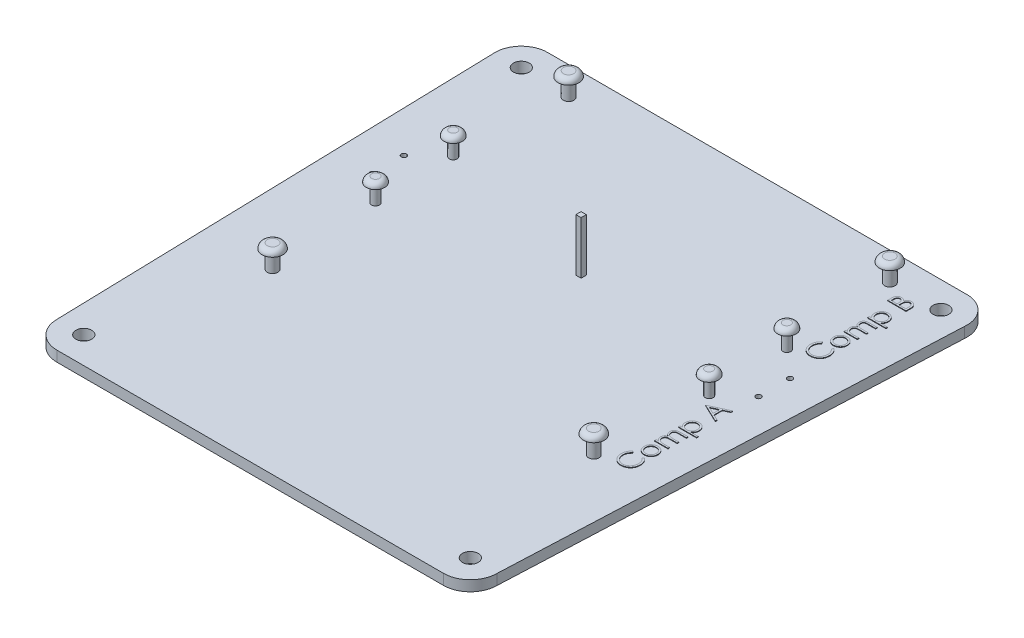
SolidWorks part; units mm, degrees
material "A-Glass Fiber"
ref_plane "Front Plane" through (0, 0, 0) normal (0, 0, 1) x (1, 0, 0)
ref_plane "Top Plane" through (0, 0, 0) normal (0, 1, 0) x (1, 0, 0)
ref_plane "Right Plane" through (0, 0, 0) normal (1, 0, 0) x (0, 0, -1)
sketch "Sketch1" plane through (0, 0, 0) normal (0, 1, 0) x (1, 0, 0)
  line L0 (40, -40) -> (-40, -40) construction
  line L1 (40, -40) -> (40, 40) construction
  line L2 (40, 40) -> (-40, 40) construction
  line L3 (-40, -40) -> (-40, 40) construction
  line L4 (40, 40) -> (-40, -40) construction
  line L5 (-40, 40) -> (40, -40) construction
  line L6 (33.9534, 31.3727) -> (33.9534, -31.6273) construction
  line L7 (33.9534, 31.3727) -> (-33.6466, 31.3727) construction
  line L8 (0, 0) -> (50000, 0) construction
  line L9 (41.2079, -57.2155) -> (44.9883, 28.1324)
  line L10 (40.0079, 33.5745) -> (-39.9621, 33.5745)
  line L11 (-44.9549, 28.3066) -> (-42.6621, -57.2155)
  line L12 (36.1079, -62.3155) -> (-37.5621, -62.3155)
  circle A0 centre (30.6704, 28.1772) radius 1
  circle A1 centre (-30.5557, 28.1772) radius 1
  circle A2 centre (-31.7456, 7.3815) radius 0.25 construction
  circle A3 centre (31.841, 7.3815) radius 0.75
  circle A4 centre (36.9534, 2.8727) radius 0.5
  circle A5 centre (36.9534, -3.1273) radius 0.5
  circle A6 centre (-36.6466, -3.1273) radius 0.5
  circle A7 centre (-36.6466, 2.8727) radius 0.5
  circle A8 centre (-31.5341, -7.6361) radius 0.75
  circle A9 centre (-30.3635, -28.4319) radius 1
  circle A10 centre (30.8626, -28.4319) radius 1
  circle A11 centre (32.0525, -7.6361) radius 0.75
  circle A12 centre (-31.7456, 7.3815) radius 0.75
  circle A13 centre (40.0079, 28.5745) radius 1.5
  circle A14 centre (-39.9621, 28.5745) radius 1.5
  circle A15 centre (-37.5621, -57.2155) radius 1.5
  circle A16 centre (36.1079, -57.2155) radius 1.5
  arc A17 (44.9883, 28.1324) -> (40.0079, 33.5745) centre (40.0079, 28.5745) ccw
  arc A18 (-44.9549, 28.3066) -> (-39.9621, 33.5745) centre (-39.9621, 28.5745) cw
  arc A19 (-37.5621, -62.3155) -> (-42.6621, -57.2155) centre (-37.5621, -57.2155) cw
  arc A20 (41.2079, -57.2155) -> (36.1079, -62.3155) centre (36.1079, -57.2155) cw
  point P28 (0, 0)
  point P56 (0.0229, -14.3705)
  dimension "D1" = 80
  dimension "D2" = 80
  dimension "D3" = 63
  dimension "D4" = 67.6
  dimension "D5" = 1
extrude "Substrate" add sketch "Sketch1" along normal blind 2
sketch "Sketch3" plane through (0, 0, 0) normal (0, -1, 0) x (1, 0, 0)
  circle A0 centre (-30.5557, -28.1772) radius 1
  circle A1 centre (30.6704, -28.1772) radius 1
  circle A2 centre (31.841, -7.3815) radius 0.75
  circle A3 centre (32.0525, 7.6361) radius 0.75
  circle A4 centre (30.8626, 28.4319) radius 1
  circle A5 centre (-30.3635, 28.4319) radius 1
  circle A6 centre (-31.5341, 7.6361) radius 0.75
  circle A7 centre (-31.7456, -7.3815) radius 0.75
extrude "Boss-Extrude4" add sketch "Sketch3" against normal blind 5.4
sketch "Sketch4" plane through (0, 5.4, 0) normal (0, 1, 0) x (1, 0, 0)
  circle A0 centre (-31.5341, -7.6361) radius 0.75 construction
  circle A1 centre (-31.7456, 7.3815) radius 0.75 construction
  circle A2 centre (-30.5557, 28.1772) radius 1 construction
  circle A3 centre (30.6704, 28.1772) radius 1 construction
  circle A4 centre (31.841, 7.3815) radius 0.75 construction
  circle A5 centre (32.0525, -7.6361) radius 0.75 construction
  circle A6 centre (30.8626, -28.4319) radius 1 construction
  circle A7 centre (-30.3635, -28.4319) radius 1 construction
  circle A8 centre (-30.3635, -28.4319) radius 2
  circle A9 centre (30.8626, -28.4319) radius 2
  circle A10 centre (32.0525, -7.6361) radius 1.75
  circle A11 centre (-31.5341, -7.6361) radius 1.75
  circle A12 centre (-31.7456, 7.3815) radius 1.75
  circle A13 centre (-30.5557, 28.1772) radius 2
  circle A14 centre (30.6704, 28.1772) radius 2
  circle A15 centre (31.841, 7.3815) radius 1.75
  dimension "D1" = 1
  dimension "D2" = 1
  dimension "D3" = 1
  dimension "D4" = 1
  dimension "D5" = 1
  dimension "D6" = 1
  dimension "D7" = 1
  dimension "D8" = 1
extrude "Boss-Extrude5" add sketch "Sketch4" along normal blind 1
fillet "Fillet1" radius 1 8 edges at (30.8626, 6.4, 30.4319) (-30.3635, 6.4, 30.4319) (-31.5341, 6.4, 9.3861) (-31.7456, 6.4, -5.6315) (32.0525, 6.4, 9.3861) (31.841, 6.4, -5.6315) (30.6704, 6.4, -26.1772) (-30.5557, 6.4, -26.1772)
sketch "Sketch5" plane through (0, 2, 0) normal (0, 1, 0) x (1, 0, 0)
  line L0 (36.9534, -40) -> (36.9534, 40) construction
  line L1 (35.7183, 40) -> (38.3748, 40) construction
  line L2 (40, 40) -> (-40, 40) construction
  line L3 (36.0585, -40) -> (37.6035, -40) construction
  line L4 (-40, -40) -> (40, -40) construction
  text T0 "         Comp A            Comp B"
extrude "Boss-Extrude6" add sketch "Sketch5" along normal blind 0.1
sketch "Sketch6" plane through (0, 2, 0) normal (0, 1, 0) x (1, 0, 0)
  line L0 (-40, 40) -> (40, -40) construction
  line L1 (40, -40) -> (40, 40) construction
  line L2 (40, 40) -> (-40, -40) construction
  line L4 (-0.5, -0.5) -> (0.5, -0.5)
  line L5 (-0.5, -0.5) -> (-0.5, 0.5)
  line L6 (-0.5, 0.5) -> (0.5, 0.5)
  line L7 (0.5, -0.5) -> (0.5, 0.5)
  line L8 (-0.5, -0.5) -> (0.5, 0.5) construction
  line L9 (-0.5, 0.5) -> (0.5, -0.5) construction
  point P4 (0, 0)
  dimension "D1" = 1
extrude "Boss-Extrude7" add sketch "Sketch6" along normal blind 10
